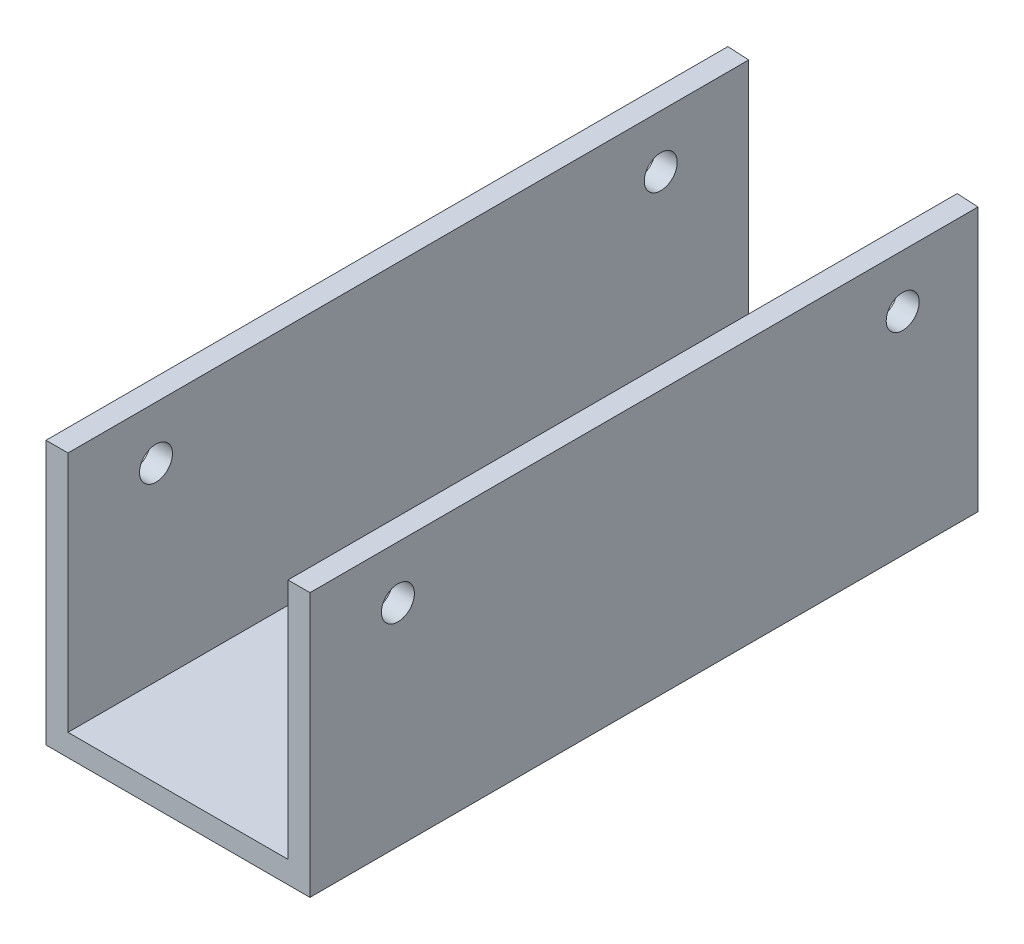
SolidWorks part; units mm, degrees
ref_plane "Front Plane" through (0, 0, 0) normal (0, 0, 1) x (1, 0, 0)
ref_plane "Top Plane" through (0, 0, 0) normal (0, 1, 0) x (1, 0, 0)
ref_plane "Right Plane" through (0, 0, 0) normal (1, 0, 0) x (0, 0, -1)
sketch "Sketch1" plane through (0, 0, 0) normal (0, 0, 1) x (1, 0, 0)
  line L0 (18.3712, 0) -> (-19.7288, 0)
  line L1 (-19.7288, 0) -> (-19.7288, 38.1)
  line L2 (-19.7288, 38.1) -> (-16.5538, 38.1)
  line L3 (-16.5538, 38.1) -> (-16.5538, 3.175)
  line L4 (-16.5538, 3.175) -> (15.1962, 3.175)
  line L5 (15.1962, 3.175) -> (15.1962, 38.1)
  line L6 (15.1962, 38.1) -> (18.3712, 38.1)
  line L7 (18.3712, 38.1) -> (18.3712, 0)
  dimension "D1" = 3.175
  dimension "D2" = 3.175
  dimension "D3" = 3.175
  dimension "D4" = 38.1
  dimension "D5" = 38.1
  dimension "D6" = 38.1
extrude "Boss-Extrude1" add sketch "Sketch1" along normal blind 98.425
sketch "Sketch2" plane through (0, 38.1, 0) normal (0, 1, 0) x (1, 0, 0)
  line L0 (-19.7288, 0) -> (18.3712, 0)
  line L1 (18.3712, 0) -> (18.3712, -1.9967)
  line L2 (18.3712, -98.425) -> (18.3712, 0) construction
  line L3 (18.3712, -1.9967) -> (-19.7288, 0)
  dimension "D1" = 3
extrude "Cut-Extrude1" cut sketch "Sketch2" against normal blind 98.425
sketch "Sketch3" plane through (18.3712, 0, 0) normal (1, 0, 0) x (0, 0, -1)
  line L0 (-98.425, 0) -> (-98.425, 38.1) construction
  line L1 (-0.1664, 3.175) -> (-0.1664, 38.1) construction
  line L2 (-98.425, 0) -> (-1.9967, 0) construction
  circle A0 centre (-12.8664, 30.48) radius 2.3813
  circle A1 centre (-85.725, 30.48) radius 2.3813
  dimension "D5" = 4.7625
  dimension "D1" = 12.7
  dimension "D2" = 12.7
  dimension "D3" = 30.48
  dimension "D4" = 30.48
extrude "Cut-Extrude2" cut sketch "Sketch3" against normal blind 98.425
